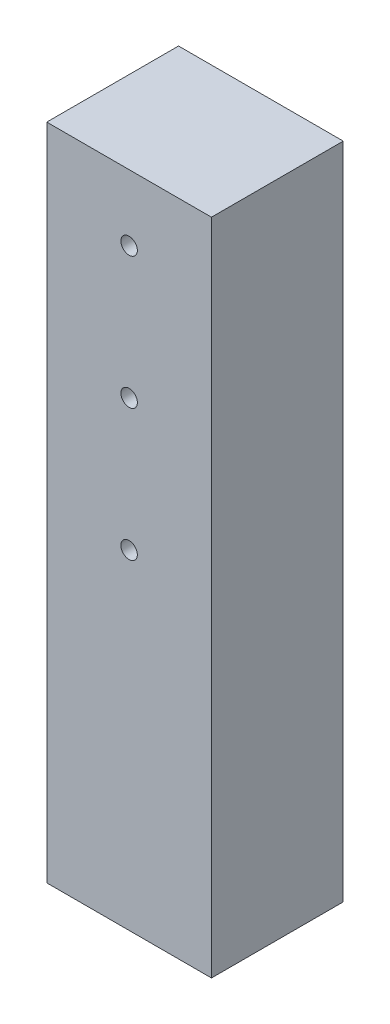
SolidWorks part; units mm, degrees
ref_plane "Front Plane" through (0, 0, 0) normal (0, 0, 1) x (1, 0, 0)
ref_plane "Top Plane" through (0, 0, 0) normal (0, 1, 0) x (1, 0, 0)
ref_plane "Right Plane" through (0, 0, 0) normal (1, 0, 0) x (0, 0, -1)
sketch "Sketch1" plane through (0, 0, 0) normal (0, 1, 0) x (1, 0, 0)
  line L0 (-17.25, 10) -> (17.25, -10) construction
  line L1 (-17.25, -10) -> (17.25, -10)
  line L2 (-17.25, -10) -> (-17.25, 10)
  line L3 (-17.25, 10) -> (17.25, 10)
  line L5 (-17.25, -10) -> (17.25, 10) construction
  line L6 (-17.25, 10) -> (17.25, -10) construction
  line L7 (-5, 5) -> (13, -5) construction
  line L8 (-5, -5) -> (13, 5) construction
  line L9 (4, 0) -> (25.25, 0) construction
  line L10 (4, 0) -> (-17.25, 0) construction
  line L12 (17.25, 10) -> (25.25, 10)
  line L14 (17.25, -10) -> (25.25, -10)
  line L15 (25.25, 10) -> (25.25, -10)
  circle A0 centre (-5, 5) radius 1.6
  arc A1 (-4.7872, -6.5858) -> (-5.2128, -6.5858) centre (-5, -5) ccw construction
  arc A2 (13.2128, -6.5858) -> (12.7872, -6.5858) centre (13, -5) ccw construction
  circle A3 centre (13, 5) radius 1.6
  circle A4 centre (-14, 4.0819) radius 1.625 construction
  circle A5 centre (-14, -4.0819) radius 1.625 construction
  circle A6 centre (-9.6025, 0) radius 1.6 construction
  circle A7 centre (-5, -5) radius 1.6
  circle A8 centre (13, -5) radius 1.6
  point P2 (0, 0)
  point P23 (4, 0)
  dimension "D1" = 21.25
extrude "Boss-Extrude1" add sketch "Sketch1" along normal blind 100
sketch "Sketch2" plane through (0, 0, 0) normal (0, -1, 0) x (1, 0, 0)
  line L0 (-5, 5) -> (13, -5) construction
  line L1 (-5, -5) -> (13, 5) construction
  line L2 (25.25, -10) -> (-17.25, -10) construction
  line L3 (16.5, 10) -> (-8.5, 10) construction
  line L4 (16.5, 10) -> (16.5, -10) construction
  line L5 (16.5, -10) -> (-8.5, -10) construction
  line L6 (-8.5, 10) -> (-8.5, -10) construction
  line L7 (16.5, 10) -> (-8.5, -10) construction
  line L8 (16.5, -10) -> (-8.5, 10) construction
  line L10 (-8.5, 10) -> (-17.25, 10)
  line L11 (-8.5, 10) -> (-8.5, -10)
  line L12 (-8.5, -10) -> (-17.25, -10)
  line L13 (-17.25, 10) -> (-17.25, -10)
  line L14 (16.5, 10) -> (25.25, 10)
  line L15 (16.5, 10) -> (16.5, -10)
  line L16 (16.5, -10) -> (25.25, -10)
  line L17 (25.25, 10) -> (25.25, -10)
  point P8 (4, 0)
  dimension "D1" = 25
extrude "Cut-Extrude1" cut sketch "Sketch2" against normal blind 100
sketch "Sketch3" plane through (0, 100, 0) normal (0, 1, 0) x (1, 0, 0)
  line L4 (16.5, 10) -> (-8.5, 10)
  line L5 (-8.5, 10) -> (-8.5, -10)
  line L6 (-8.5, -10) -> (16.5, -10)
  line L7 (16.5, -10) -> (16.5, 10)
  line L8 (16.5, 10) -> (-8.5, 10)
  line L9 (-8.5, 10) -> (-8.5, -10)
  line L10 (-8.5, -10) -> (16.5, -10)
  line L11 (16.5, -10) -> (16.5, 10)
  dimension "D1" = 0
extrude "Boss-Extrude2" add sketch "Sketch3" against normal blind 60
sketch "Sketch4" plane through (0, 0, 10) normal (0, 0, 1) x (1, 0, 0)
  line L0 (4, 100) -> (4, 0) construction
  line L1 (-8.5, 100) -> (16.5, 100) construction
  line L2 (-8.5, 0) -> (16.5, 0) construction
  line L3 (4, 70) -> (4, 50) construction
  line L4 (4, 90) -> (4, 70) construction
  circle A0 centre (4, 50) radius 1.25
  circle A1 centre (4, 70) radius 1.25
  circle A2 centre (4, 90) radius 1.25
  dimension "D1" = 2.5
  dimension "D2" = 2.5
  dimension "D3" = 2.5
  dimension "D4" = 20
  dimension "D5" = 20
extrude "Cut-Extrude2" cut sketch "Sketch4" against normal blind 60
sketch "Sketch5" plane through (0, 0, 10) normal (0, 0, 1) x (1, 0, 0)
  line L0 (4, 100) -> (4, 90) construction
  line L1 (-8.5, 100) -> (16.5, 100) construction
  line L2 (4, 90) -> (4, 70) construction
  line L3 (4, 70) -> (4, 50) construction
  line L4 (4, 50) -> (4, 30) construction
  line L5 (4, 100) -> (24, 100)
  line L6 (24, 100) -> (24, 30)
  line L7 (24, 30) -> (4, 30)
  line L8 (4, 100) -> (-16, 100)
  line L9 (-16, 100) -> (-16, 30)
  line L10 (-16, 30) -> (4, 30)
  circle A0 centre (4, 90) radius 1.25
  circle A1 centre (4, 70) radius 1.25
  circle A2 centre (4, 50) radius 1.25
  dimension "D1" = 20
  dimension "D2" = 20
  dimension "D3" = 20
